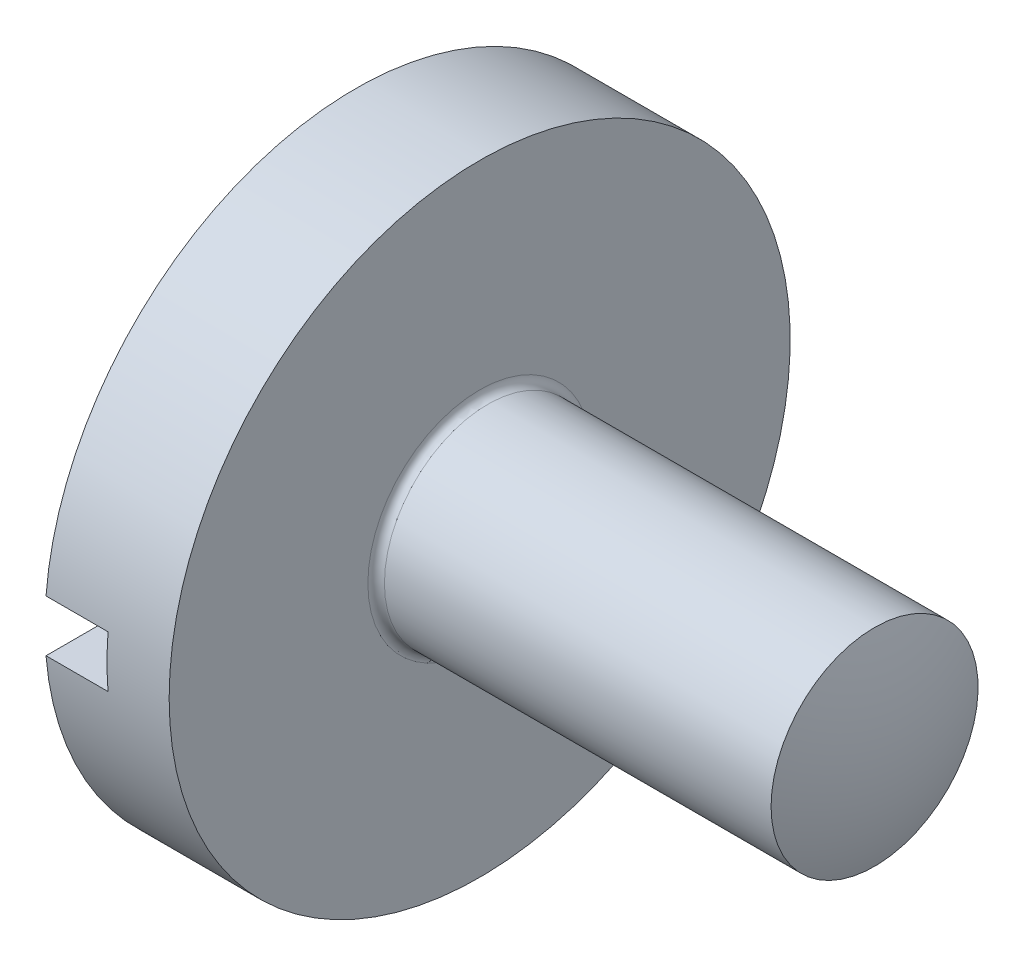
SolidWorks part; units mm, degrees
ref_plane "Front" through (0, 0, 0) normal (0, 0, 1) x (1, 0, 0)
ref_plane "Top" through (0, 0, 0) normal (0, 1, 0) x (1, 0, 0)
ref_plane "Right" through (0, 0, 0) normal (1, 0, 0) x (0, 0, -1)
sketch "Sketch1" plane through (0, 0, 0) normal (0, 0, 1) x (1, 0, 0)
  line L0 (0, 0) -> (0, 15)
  line L1 (0, 15) -> (6, 15)
  line L2 (6, 15) -> (6, 5.4)
  line L3 (6.4, 5) -> (25.0767, 5)
  line L4 (-64.3562, 0) -> (99.7857, 0) construction
  line L5 (0, 0) -> (26, 0)
  line L6 (9, 5) -> (9, 0) construction
  arc A0 (26, 0) -> (25.0767, 5) centre (12, 0) ccw
  arc A1 (6.4, 5) -> (6, 5.4) centre (6.4, 5.4) cw
revolve "Base" add sketch "Sketch1" angle 360 about L4
cosmetic thread "ThreadCosmetic1" [suppressed] parameters "D1"=17, "THD_MINOR"=7.5
sketch "Sketch2" plane through (0, 0, 0) normal (0, 0, 1) x (1, 0, 0)
  line L0 (30.8988, 0) -> (-6.4914, 0) construction
  line L1 (0, 1.25) -> (3, 1.25)
  line L2 (0, 1.25) -> (0, -1.25)
  line L3 (0, -1.25) -> (3, -1.25)
  line L4 (3, 1.25) -> (3, -1.25)
  line L7 (0, 15) -> (0, -15) construction
  dimension "n" = 2.5
  dimension "t" = 3
extrude "Slot" cut sketch "Sketch2" against normal through all and the other way through all
sketch "Sketch3" plane through (0, 0, 0) normal (0, 0, 1) x (1, 0, 0)
  line L0 (25.0767, 3.9175) -> (25.7017, 5)
  line L1 (25.7017, 5) -> (25.7017, 6.25)
  line L2 (25.7017, 6.25) -> (24.4517, 6.25)
  line L3 (24.4517, 6.25) -> (24.4517, 5)
  line L4 (24.4517, 5) -> (25.0767, 3.9175)
  line L5 (25.0767, 5) -> (25.0767, -5) construction
  line L6 (0, 0) -> (31.7128, 0) construction
  dimension "D1" = 10
  dimension "D2" = 1.25
revolve "Cut-Revolve10" [suppressed] cut sketch "Sketch3" angle 360 about L6
pattern_linear "LPattern10" [suppressed] count 11 spacing 1.5 along (-1, 0, 0) of bodies 103
equation "\"D1@ThreadCosmetic1\" = \"l@Sketch1\" - \"a@Sketch1\""
equation "\"D1@Sketch3\" = \"d@Sketch1\""
equation "\"D2@Sketch3\" =  ( \"d@Sketch1\" - \"THD_MINOR@ThreadCosmetic1\" )  / 2"
equation "\"D3@LPattern10\" = \"D2@Sketch3\" * 1.2"
equation "\"D1@LPattern10\" = \"D1@ThreadCosmetic1\" / \"D3@LPattern10\""
